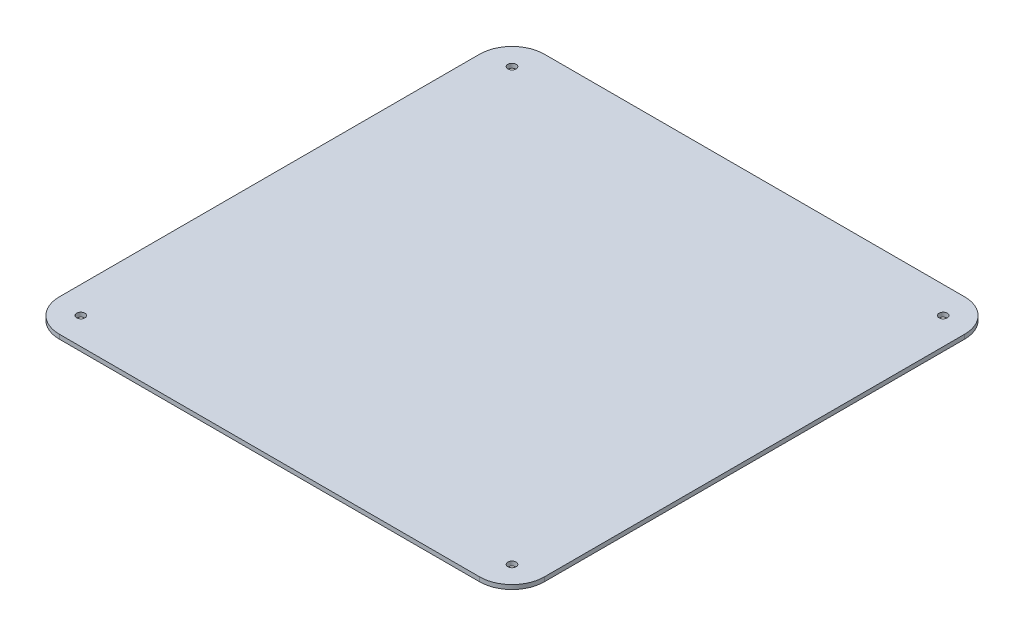
SolidWorks part; units mm, degrees
ref_plane "Front Plane" through (0, 0, 0) normal (0, 0, 1) x (1, 0, 0)
ref_plane "Top Plane" through (0, 0, 0) normal (0, 1, 0) x (1, 0, 0)
ref_plane "Right Plane" through (0, 0, 0) normal (1, 0, 0) x (0, 0, -1)
sketch "Sketch1" plane through (0, 0, 0) normal (0, 1, 0) x (1, 0, 0)
  line L1 (-225, -225) -> (225, -225)
  line L2 (-225, -225) -> (-225, 225)
  line L3 (-225, 225) -> (225, 225)
  line L4 (225, -225) -> (225, 225)
  line L5 (-225, -225) -> (225, 225) construction
  line L6 (-225, 225) -> (225, -225) construction
  point P0 (0, 0)
  dimension "D1" = 450
  dimension "D2" = 450
base flange "Base-Flange1" sketch "Sketch1" thickness 4 reverse thickness direction no parameters "D1"=5.715
fillet "Fillet1" radius 30 4 edges at (225, -2, -225) (-225, -2, -225) (-225, -2, 225) (225, -2, 225)
hole_wizard "M7 Clearance Hole1" positions "Sketch7" profile "Sketch8" hole size "M7" standard "ANSI Metric" end condition through all
sketch "Sketch7" plane through (0, 0, 0) normal (0, 1, 0) x (1, 0, 0)
  line L1 (-200, -200) -> (200, -200) construction
  line L2 (-200, -200) -> (-200, 200) construction
  line L3 (-200, 200) -> (200, 200) construction
  line L4 (200, -200) -> (200, 200) construction
  line L5 (-200, -200) -> (200, 200) construction
  line L6 (-200, 200) -> (200, -200) construction
  point P2 (200, 200)
  point P149 (-200, -200)
  point P150 (-200, 200)
  point P151 (200, -200)
  point P166 (0, 0)
  dimension "D1" = 400
sketch "Sketch8" plane through (200, 0, -200) normal (1, 0, 0) x (0, 0, 1)
  line L0 (0, 0) -> (0, 4)
  line L1 (0, 4) -> (3.8, 4)
  line L2 (3.8, 4) -> (3.8, 0)
  line L5 (3.8, 0) -> (0, 0)
  line L11 (0, -6.35) -> (0, 107.95) construction
  dimension "Thru Hole Dia." = 7.6
  dimension "Thru Hole Depth" = 4
sketch "Bend-Lines1" [suppressed] plane through (0, 0, 0) normal (0, 1, 0) x (1, 0, 0)
sketch "Bounding-Box1" [suppressed] plane through (0, 0, 0) normal (0, 1, 0) x (1, 0, 0)
sheet metal parameters "Sheet-Metal1" thickness 4 parameters "D1"=5.715
flat pattern "Flat-Pattern1" [suppressed]
sketch "Bend-Lines2" plane through (0, 0, 0) normal (0, 1, 0) x (1, 0, 0)
sketch3d "Bounding-Box2" [suppressed]
  line L0 (-225, 225, 0) -> (225, 225, 0) construction
  line L1 (-225, -225, 0) -> (225, -225, 0) construction
  line L2 (-225, 225, 0) -> (-225, -225, 0) construction
  line L3 (225, 225, 0) -> (225, -225, 0) construction
sheet metal parameters "Sheet-Metal2" thickness 4 parameters "D1"=5.715
flat pattern "Flat-Pattern1"
sketch "Bend-Lines2" plane through (0, 0, 0) normal (0, 1, 0) x (1, 0, 0)
sketch3d "Bounding-Box2" [suppressed]
  line L0 (-225, 225, 0) -> (225, 225, 0) construction
  line L1 (-225, -225, 0) -> (225, -225, 0) construction
  line L2 (-225, 225, 0) -> (-225, -225, 0) construction
  line L3 (225, 225, 0) -> (225, -225, 0) construction
